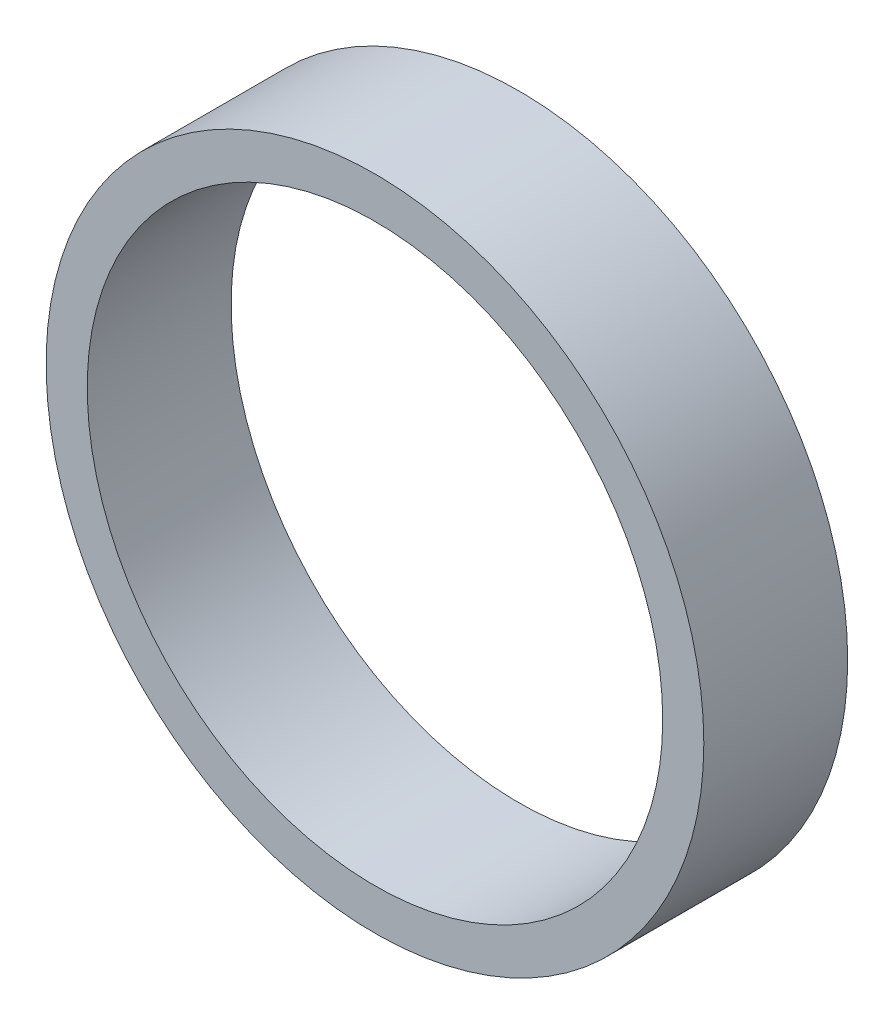
SolidWorks part; units mm, degrees
material "Leaded Commercial Bronze"
ref_plane "Front Plane" through (0, 0, 0) normal (0, 0, 1) x (1, 0, 0)
ref_plane "Top Plane" through (0, 0, 0) normal (0, 1, 0) x (1, 0, 0)
ref_plane "Right Plane" through (0, 0, 0) normal (1, 0, 0) x (0, 0, -1)
sketch "Sketch1" plane through (0, 0, 0) normal (0, 0, 1) x (1, 0, 0)
  circle A0 centre (0, 0) radius 50.8
  circle A1 centre (0, 0) radius 44.45
  dimension "D1" = 101.6
  dimension "D2" = 88.9
extrude "Boss-Extrude1" add sketch "Sketch1" along normal mid plane 22.225
sketch "Sketch2" plane through (0, 0, 0) normal (0, 1, 0) x (1, 0, 0)
  circle A0 centre (0, 0) radius 1.5875
  point P2 (0, 0)
  dimension "D1" = 3.175
extrude "Cut-Extrude1" [suppressed] cut sketch "Sketch2" along normal through all
pattern_circular "CirPattern1" [suppressed] count 4 over 360 of bodies 102
